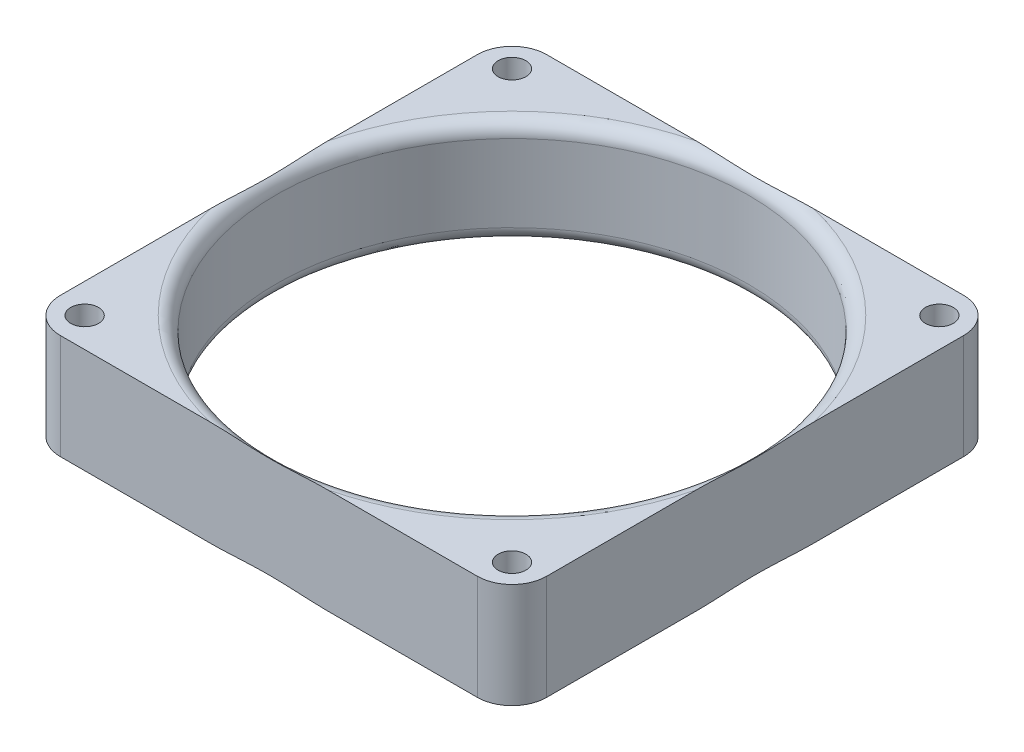
SolidWorks part; units mm, degrees
ref_plane "Спереди" through (0, 0, 0) normal (0, 0, 1) x (1, 0, 0)
ref_plane "Сверху" through (0, 0, 0) normal (0, 1, 0) x (1, 0, 0)
ref_plane "Справа" through (0, 0, 0) normal (1, 0, 0) x (0, 0, -1)
sketch "Эскиз1" plane through (0, 0, 0) normal (0, 1, 0) x (1, 0, 0)
  line L0 (0, 0) -> (0, 35) construction
  line L1 (-35, -35) -> (35, -35)
  line L2 (-35, -35) -> (-35, 35)
  line L3 (-35, 35) -> (35, 35)
  line L4 (35, -35) -> (35, 35)
  line L5 (-35, -35) -> (35, 35) construction
  line L6 (-35, 35) -> (35, -35) construction
  circle A0 centre (30.75, 30.75) radius 2
  circle A1 centre (0, 0) radius 34
  circle A2 centre (30.75, -30.75) radius 2
  circle A3 centre (-30.75, -30.75) radius 2
  circle A4 centre (-30.75, 30.75) radius 2
  point P0 (0, 0)
  point P20 (0, 0)
  dimension "D2" = 4
  dimension "D4" = 68
  dimension "D1" = 70
  dimension "D3" = 30.75
  dimension "D5" = 4
extrude "Бобышка-Вытянуть1" add sketch "Эскиз1" along normal blind 15.1
fillet "Скругление1" radius 5 4 edges at (-35, 7.55, -35) (-35, 7.55, 35) (35, 7.55, 35) (35, 7.55, -35)
fillet "Скругление2" radius 2 2 edges at (0, 0, 34) (0, 15.1, 34)
